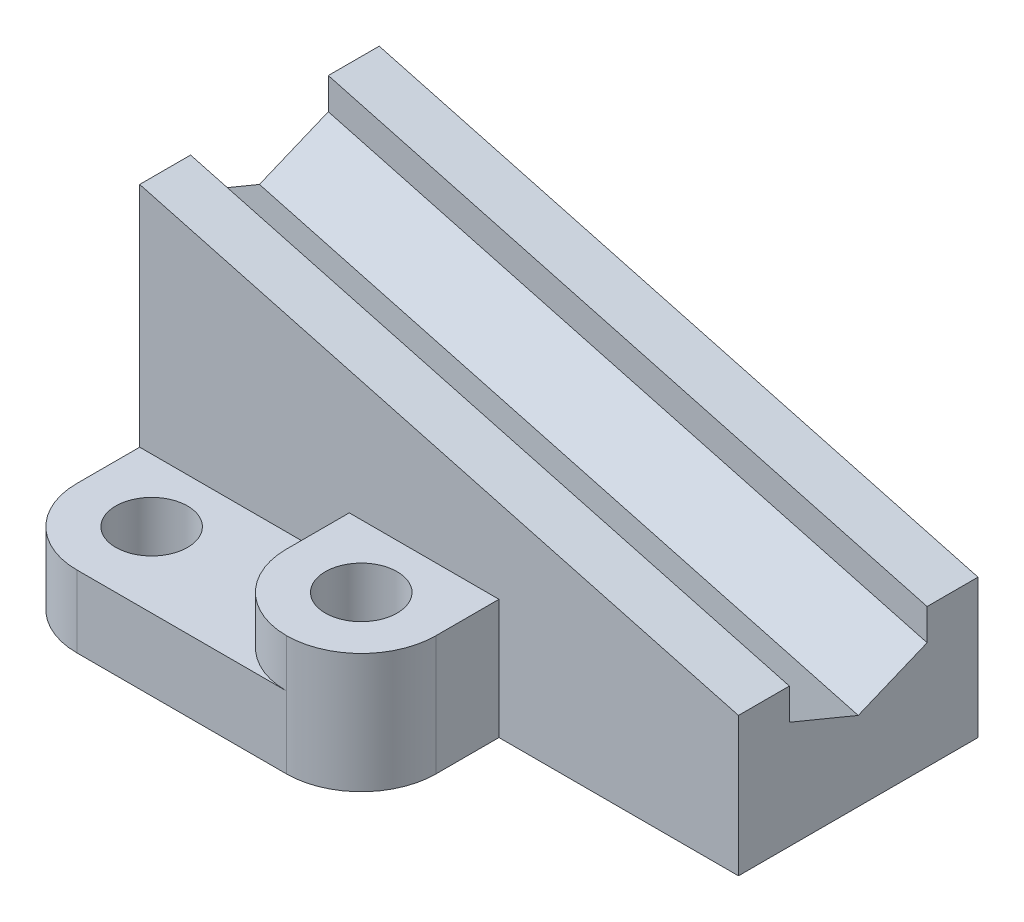
SolidWorks part; units mm, degrees
note: The reader was unsure of these and kept them because the rebuilt part matched: shared geometry of "Sketch1<4>", "Sketch1<5>".
material "1060 합금"
ref_plane "정면" through (0, 0, 0) normal (0, 0, 1) x (1, 0, 0)
ref_plane "윗면" through (0, 0, 0) normal (0, 1, 0) x (1, 0, 0)
ref_plane "우측면" through (0, 0, 0) normal (1, 0, 0) x (0, 0, -1)
sketch "Sketch1" plane through (0, 0, 0) normal (0, 1, 0) x (1, 0, 0)
  line L1 (0, 0) -> (100, 0)
  line L2 (0, 0) -> (0, 40)
  line L3 (0, 40) -> (100, 40)
  line L4 (100, 0) -> (100, 40)
  line L5 (0, 0) -> (35, 0)
  line L6 (0, 0) -> (0, -23)
  line L7 (0, -23) -> (35, -23)
  line L8 (35, 0) -> (35, -23)
  line L9 (35, -23) -> (60, -23)
  line L10 (35, -23) -> (35, 0)
  line L11 (35, 0) -> (60, 0)
  line L12 (60, -23) -> (60, 0)
  dimension "D1" = 63
  dimension "D2" = 100
  dimension "D3" = 60
  dimension "D4" = 23
  dimension "D5" = 25
extrude "Boss-Extrude1" add sketch "Sketch1" along normal blind 50 contours L1 L4 L3 L2
extrude "Boss-Extrude2" add sketch "Sketch1<4>" along normal blind 12 contours L8 L1 L6 L7
sketch "Sketch1<4>" plane through (0, 0, 0) normal (0, 1, 0) x (1, 0, 0) same geometry as "Sketch1"
extrude "Boss-Extrude3" add sketch "Sketch1<5>" along normal blind 20 contours L9 L12 L1 L8
sketch "Sketch1<5>" plane through (0, 0, 0) normal (0, 1, 0) x (1, 0, 0) same geometry as "Sketch1"
fillet "Fillet1" radius 12.5 3 edges at (60, 10, 23) (35, 16, 23) (0, 6, 23)
sketch "Sketch2" plane through (0, 0, 0) normal (0, 0, 1) x (1, 0, 0)
  line L0 (0, 50) -> (100, 23.2051)
  line L1 (100, 50) -> (100, 0) construction
  line L2 (100, 23.2051) -> (100, 50)
  line L3 (100, 50) -> (0, 50)
  dimension "D1" = 15
extrude "Cut-Extrude1" cut sketch "Sketch2" against normal through all
sketch "Sketch4" plane through (0, 0, 0) normal (-1, 0, 0) x (0, 0, 1)
  line L0 (-20, 52.8525) -> (-20, -4.5076) construction
  line L1 (-31.5, 50) -> (-31.5, 44.7635)
  line L2 (0, 50) -> (-40, 50) construction
  line L3 (-31.5, 44.7635) -> (-20, 40)
  line L4 (-31.5, 50) -> (-8.5, 50)
  line L5 (-8.5, 50) -> (-8.5, 44.7635)
  line L6 (-8.5, 44.7635) -> (-20, 40)
  point P9 (-20, 50)
  dimension "D1" = 23
  dimension "D2" = 10
  dimension "D3" = 135
extrude "Cut-Extrude2" cut sketch "Sketch4" along direction (0.9659, -0.2588, 0) on the side against the normal through all
hole_wizard "Ø12.0 (12) Diameter Hole1" positions "3DSketch1" profile "Sketch5" hole size "Ø12.0" standard "Ansi Metric" end condition up to next
sketch3d "3DSketch1"
  line L0 (12.5, 0, 10.5) -> (12.5, 12, 10.5) construction
  line L1 (47.5, 20, 10.5) -> (47.5, 12, 10.5) construction
  point P0 (12.5, 12, 10.5)
  point P4 (47.5, 20, 10.5)
sketch "Sketch5" plane through (12.5, 12, 10.5) normal (1, 0, 0) x (0, 0, 1)
  line L0 (0, 0) -> (0, 12)
  line L1 (0, 12) -> (6, 12)
  line L2 (6, 12) -> (6, 0)
  line L5 (6, 0) -> (0, 0)
  line L11 (0, -6.35) -> (0, 107.95) construction
  dimension "관통 구멍 지름" = 12
  dimension "관통 구멍 깊이" = 12
